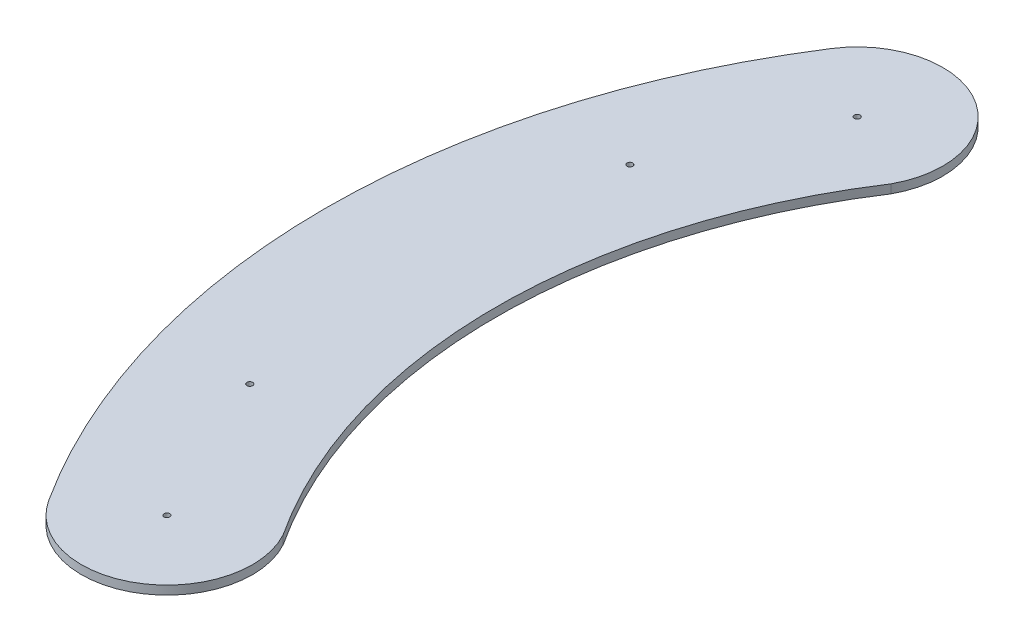
SolidWorks part; units mm, degrees
ref_plane "Plan de face" through (0, 0, 0) normal (0, 0, 1) x (1, 0, 0)
ref_plane "Plan de dessus" through (0, 0, 0) normal (0, 1, 0) x (1, 0, 0)
ref_plane "Plan de droite" through (0, 0, 0) normal (1, 0, 0) x (0, 0, -1)
sketch "Esquisse1" plane through (0, 0, 0) normal (0, 1, 0) x (1, 0, 0)
  line L1 (-201.1163, -148.5) -> (201.1163, -148.5) construction
  line L2 (-201.1163, -148.5) -> (-201.1163, 148.5) construction
  line L3 (-201.1163, 148.5) -> (201.1163, 148.5) construction
  line L4 (201.1163, -148.5) -> (201.1163, 148.5) construction
  line L5 (-201.1163, -148.5) -> (201.1163, 148.5) construction
  line L6 (-201.1163, 148.5) -> (201.1163, -148.5) construction
  circle A0 centre (0, 0) radius 250 construction
  circle A1 centre (-185.632, 119) radius 29.5 construction
  circle A2 centre (-210.5418, 65.5163) radius 29.5 construction
  circle A3 centre (-210.5418, -65.5163) radius 29.5 construction
  circle A4 centre (-185.632, -119) radius 29.5 construction
  circle A5 centre (185.632, -119) radius 29.5 construction
  circle A6 centre (210.5418, -65.5163) radius 29.5 construction
  circle A7 centre (210.5418, 65.5163) radius 29.5 construction
  circle A8 centre (185.632, 119) radius 29.5 construction
  arc A9 (-159.7751, -104.799) -> (-159.7751, 104.799) centre (0, 0) cw
  arc A10 (-210.4672, -134.9206) -> (-210.4672, 134.9206) centre (0, 0) cw
  arc A11 (-210.4672, 134.9206) -> (-159.7751, 104.799) centre (-185.632, 119) cw
  arc A12 (-210.4672, -134.9206) -> (-159.7751, -104.799) centre (-185.632, -119) ccw
  circle A13 centre (-185.632, 119) radius 1
  circle A14 centre (-210.5418, 65.5163) radius 1
  circle A15 centre (-210.5418, -65.5163) radius 1
  circle A16 centre (-185.632, -119) radius 1
  dimension "D1" = 500
  dimension "D3" = 59
  dimension "D4" = 2
  dimension "D2" = 297
extrude "Boss.-Extru.1" add sketch "Esquisse1" along normal blind 3
